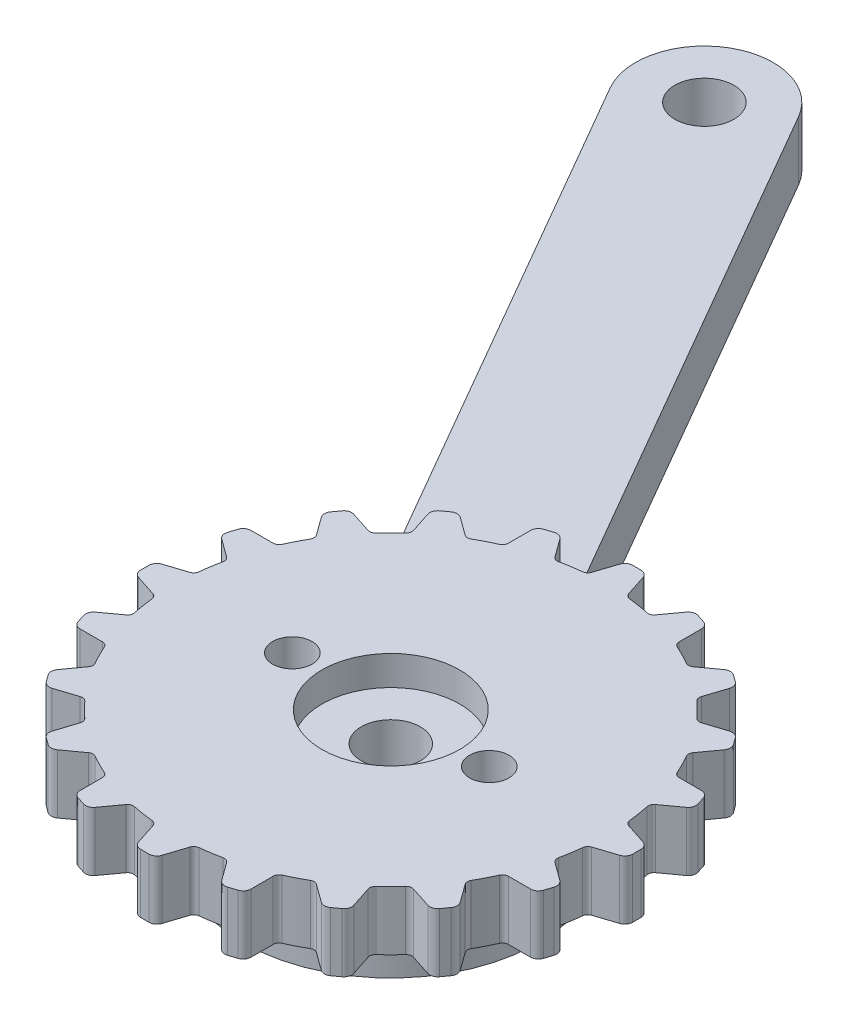
SolidWorks part; units mm, degrees
material "ABS"
ref_plane "Front Plane" through (0, 0, 0) normal (0, 0, 1) x (1, 0, 0)
ref_plane "Top Plane" through (0, 0, 0) normal (0, 1, 0) x (1, 0, 0)
ref_plane "Right Plane" through (0, 0, 0) normal (1, 0, 0) x (0, 0, -1)
sketch "Sketch1" plane through (0, 0, 0) normal (0, 1, 0) x (1, 0, 0)
  line L0 (0, 12.5) -> (0, -12.5) construction
  line L1 (-1, 10.9545) -> (-0.5899, 12.2138)
  line L2 (-0.2096, 12.49) -> (0.2096, 12.49)
  line L3 (0.5899, 12.2138) -> (1, 10.9545)
  circle A0 centre (0, 0) radius 12.5
  circle A1 centre (0, 0) radius 11
  arc A2 (0.2096, 12.49) -> (0.5899, 12.2138) centre (0.2096, 12.09) cw
  arc A3 (-0.5899, 12.2138) -> (-0.2096, 12.49) centre (-0.2096, 12.09) cw
  circle A4 centre (0, 0) radius 3.5
  circle A5 centre (-5, 0) radius 1
  circle A6 centre (5, 0) radius 1
  circle A7 centre (0, 0) radius 11.75 construction
  circle A8 centre (0, 0) radius 7.5
  point P12 (0.5, 12.49)
  point P15 (-0.5, 12.49)
  dimension "D1" = 25
  dimension "D2" = 22
  dimension "D3" = 1
  dimension "D6" = 0.4
  dimension "D7" = 7
  dimension "D8" = 2
  dimension "D11" = 2
  dimension "D12" = 23.5
  dimension "D13" = 15
  dimension "D4" = 1
  dimension "D5" = 0.5
  dimension "D9" = 5
  dimension "D10" = 5
extrude "Boss-Extrude1" add sketch "Sketch1" along normal mid plane 3 contours L0 A1 | A1 L0 | A8 A4 A5 A6 region at (0, 0, -10.6889) region at (-7.2879, 0, 0)
extrude "Boss-Extrude2" add sketch "Sketch1<3>" along normal mid plane 3 contours L0 L2 A3 L1 A1 region at (0, 0, -11.6439)
sketch "Sketch1<3>" plane through (0, 0, 0) normal (0, 1, 0) x (1, 0, 0) same geometry as "Sketch1"
fillet "Fillet1" radius 0.3 2 edges at (1, 0, -10.9545) (-1, 0, -10.9545)
pattern_circular "CirPattern1" count 20 over 360 about axis through (0, 1.5, 0) along (0, 1, 0) of "Boss-Extrude2", "Fillet1"
sketch "Sketch2" plane through (0, -1.5, 0) normal (0, -1, 0) x (1, 0, 0)
  line L0 (1.75, -3.0311) -> (21.75, -37.6721) construction
  line L1 (3.0311, 1.75) -> (24.7811, -35.9221) construction
  line L2 (-3.0311, -1.75) -> (18.7189, -39.4221) construction
  line L3 (1.75, -3.0311) -> (-23.1124, -3.0311) construction
  line L4 (0, 16.2083) -> (0, -16.8332) construction
  line L5 (-1.75, -3.0311) -> (-21.75, -37.6721) construction
  line L6 (3.0311, -1.75) -> (-18.7189, -39.4221)
  line L7 (-3.0311, 1.75) -> (-24.7811, -35.9221)
  circle A0 centre (0, 0) radius 3.5 construction
  arc A2 (18.7189, -39.4221) -> (24.7811, -35.9221) centre (21.75, -37.6721) ccw construction
  arc A3 (-3.0311, -1.75) -> (3.0311, 1.75) centre (0, 0) ccw construction
  arc A4 (-18.7189, -39.4221) -> (-24.7811, -35.9221) centre (-21.75, -37.6721) cw
  arc A5 (-3.0311, 1.75) -> (3.0311, -1.75) centre (0, 0) ccw
  dimension "D2" = 3.5
  dimension "D3" = 40
  dimension "D4" = 40
  dimension "D6" = 60
extrude "Boss-Extrude3" add sketch "Sketch2" along normal blind 3 contours A3 L2 A2 L1 | L6 L7 A4 region at (-12.2494, -1.5, -21.2167)
sketch "Sketch3" plane through (0, -1.5, 0) normal (0, 1, 0) x (1, 0, 0)
  circle A0 centre (-21.75, 37.6721) radius 1.5
  dimension "D1" = 3
extrude "Cut-Extrude1" cut sketch "Sketch3" against normal through all
extrude "Boss-Extrude4" add sketch "Sketch1<4>" against normal blind 5 contours A8
sketch "Sketch1<4>" plane through (0, 0, 0) normal (0, 1, 0) x (1, 0, 0) same geometry as "Sketch1"
sketch "Sketch4" plane through (0, -5, 0) normal (0, -1, 0) x (1, 0, 0)
  circle A0 centre (0, 0) radius 1.5
  dimension "D1" = 3
extrude "Cut-Extrude2" cut sketch "Sketch4" against normal through all both and the other way through all
